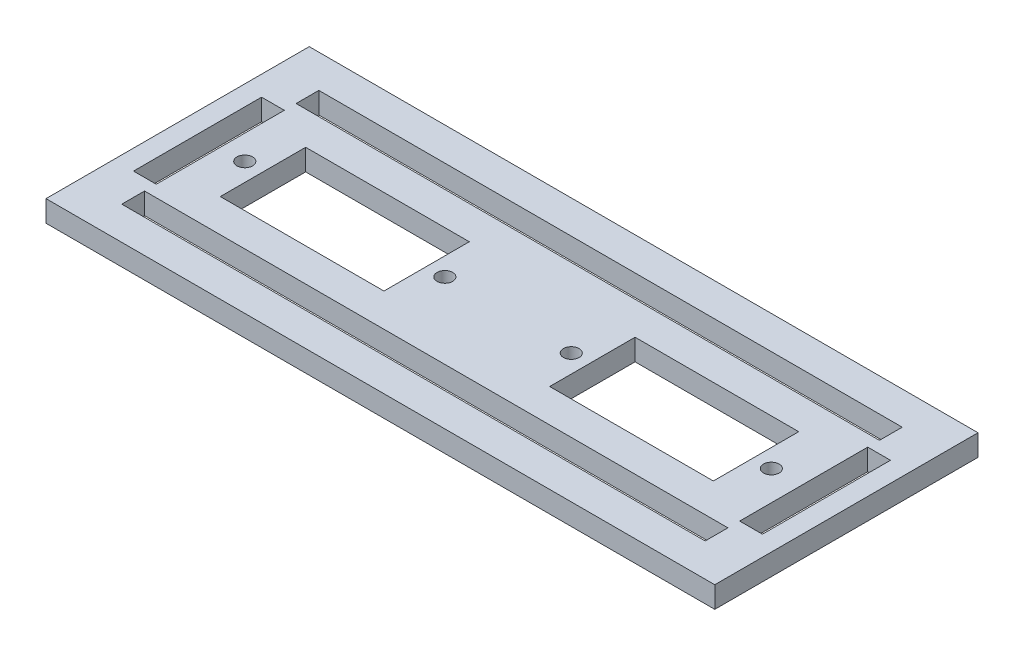
SolidWorks part; units mm, degrees
ref_plane "Front" through (0, 0, 0) normal (0, 0, 1) x (1, 0, 0)
ref_plane "Top" through (0, 0, 0) normal (0, 1, 0) x (1, 0, 0)
ref_plane "Right" through (0, 0, 0) normal (1, 0, 0) x (0, 0, -1)
sketch "Esboço1" plane through (0, 0, 0) normal (0, 1, 0) x (1, 0, 0)
  line L1 (-31.5761, 34.668) -> (62.4239, 34.668)
  line L2 (-31.5761, 34.668) -> (-31.5761, -2.332)
  line L3 (-31.5761, -2.332) -> (62.4239, -2.332)
  line L4 (62.4239, 34.668) -> (62.4239, -2.332)
  line L5 (-31.5761, 34.668) -> (62.4239, -2.332) construction
  line L6 (-31.5761, -2.332) -> (62.4239, 34.668) construction
  point P0 (15.4239, 16.168)
  dimension "D1" = 37
  dimension "D2" = 94
extrude "Ressalto-extrusão1" add sketch "Esboço1" along normal blind 3
sketch "Esboço2" plane through (0, 3, 0) normal (0, 1, 0) x (1, 0, 0)
  line L1 (56.4239, 5.518) -> (-25.5761, 5.518)
  line L2 (56.4239, 5.518) -> (56.4239, 2.318)
  line L3 (56.4239, 2.318) -> (-25.5761, 2.318)
  line L4 (-25.5761, 5.518) -> (-25.5761, 2.318)
  line L5 (56.4239, 30.018) -> (-25.5761, 30.018)
  line L8 (56.4239, 26.818) -> (-25.5761, 26.818)
  line L13 (-28.7761, 25.168) -> (-25.5761, 25.168)
  line L14 (-28.7761, 25.168) -> (-28.7761, 7.168)
  line L15 (-28.7761, 7.168) -> (-25.5761, 7.168)
  line L16 (-25.5761, 25.168) -> (-25.5761, 7.168)
  line L18 (56.4239, 30.018) -> (56.4239, 26.818)
  line L24 (-31.5761, -2.332) -> (62.4239, -2.332) construction
  line L25 (3.4239, 10.168) -> (-19.5761, 10.168)
  line L26 (3.4239, 10.168) -> (3.4239, 22.168)
  line L27 (3.4239, 22.168) -> (-19.5761, 22.168)
  line L28 (-19.5761, 10.168) -> (-19.5761, 22.168)
  line L29 (56.4239, 25.168) -> (59.6239, 25.168)
  line L31 (62.4239, 34.668) -> (-31.5761, 34.668) construction
  line L32 (-31.5761, 34.668) -> (-31.5761, -2.332) construction
  line L34 (62.4239, -2.332) -> (62.4239, 34.668) construction
  line L37 (56.4239, 25.168) -> (56.4239, 7.168)
  line L38 (56.4239, 7.168) -> (59.6239, 7.168)
  line L39 (59.6239, 25.168) -> (59.6239, 7.168)
  line L40 (49.6956, 10.196) -> (26.6956, 10.196)
  line L41 (49.6956, 10.196) -> (49.6956, 22.196)
  line L42 (49.6956, 22.196) -> (26.6956, 22.196)
  line L43 (26.6956, 10.196) -> (26.6956, 22.196)
  line L44 (-25.5761, 26.818) -> (-25.5761, 30.018)
  circle A2 centre (5.9839, 16.168) radius 1.1
  circle A3 centre (-22.1361, 16.168) radius 1.1
  circle A4 centre (52.2556, 15.7865) radius 1.1
  circle A5 centre (24.1356, 15.7865) radius 1.1
  point P0 (-8.0761, 3.918)
  point P5 (-8.0761, 28.418)
  point P10 (-27.693, 16.168)
  point P36 (3.4239, 16.168)
  point P37 (-19.5761, 16.168)
  point P42 (-8.0761, 16.168)
  point P54 (49.6956, 16.196)
  point P55 (26.6956, 16.196)
  dimension "D4" = 2.56
  dimension "D17" = 2.56
  dimension "D29" = 2.56
  dimension "D30" = 2.56
  dimension "D1" = 12.5
  dimension "D5" = 2.8
  dimension "D6" = 6
  dimension "D7" = 4.65
  dimension "D8" = 9.5
  dimension "D9" = 3.2
  dimension "D10" = 9.5
  dimension "D11" = 6
  dimension "D14" = 23
  dimension "D15" = 6
  dimension "D16" = 9.5
  dimension "D20" = 3.2
  dimension "D21" = 9.5
  dimension "D22" = 12
  dimension "D23" = 3.2
  dimension "D25" = 3.2
  dimension "D26" = 23
  dimension "D27" = 12
  dimension "D28" = 6
  dimension "D33" = 21.3
extrude "Corte-extrusão2" cut sketch "Esboço2" against normal blind 3 contours L14 L13 L16 L15 | L8 L44 L5 L18 | L2 L1 L4 L3
extrude "Corte-extrusão4" cut sketch "Esboço2<5>" against normal blind 10
sketch "Esboço2<5>" plane through (0, 3, 0) normal (0, 1, 0) x (1, 0, 0) same geometry as "Esboço2"
